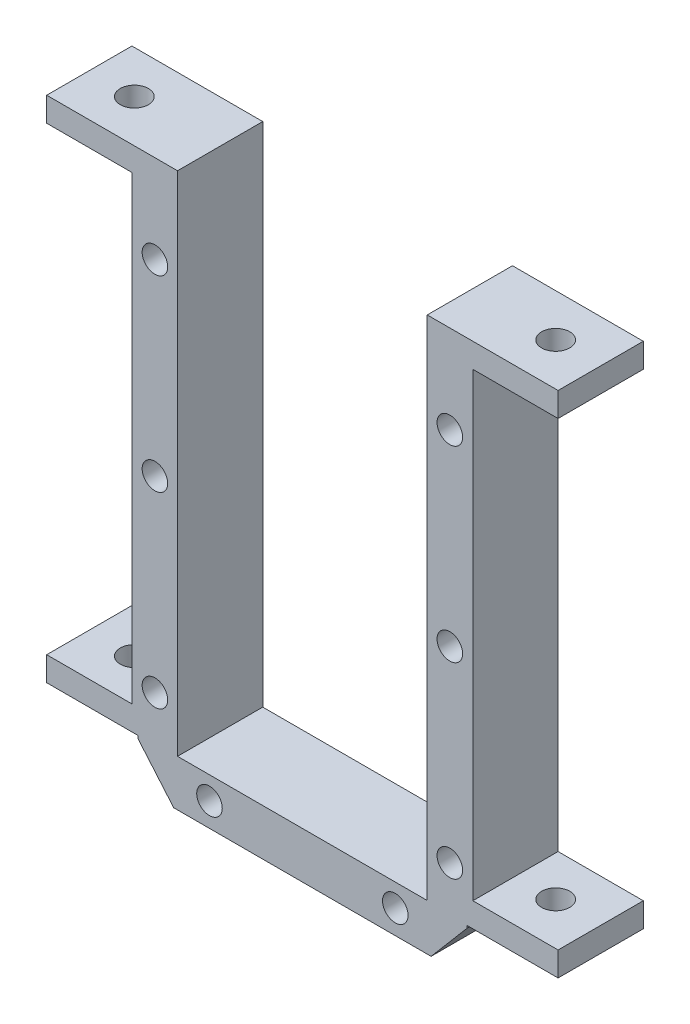
SolidWorks part; units mm, degrees
material "AISI 1035 Acier (SS)"
ref_plane "Front Plane" through (0, 0, 0) normal (0, 0, 1) x (1, 0, 0)
ref_plane "Top Plane" through (0, 0, 0) normal (0, 1, 0) x (1, 0, 0)
ref_plane "Right Plane" through (0, 0, 0) normal (1, 0, 0) x (0, 0, -1)
sketch "Sketch1" plane through (0, 0, 0) normal (0, 0, 1) x (1, 0, 0)
  line L1 (-20.1, 32.55) -> (19.9, 32.55)
  line L2 (-20.1, 32.55) -> (-20.1, -32.55)
  line L3 (-20.1, -32.55) -> (19.9, -32.55)
  line L4 (19.9, 32.55) -> (19.9, -32.55)
  point P0 (0, 0)
  dimension "D1" = 40
  dimension "D2" = 65.1
extrude "Boss-Extrude1" add sketch "Sketch1" along normal blind 10
sketch "Sketch2" plane through (0, 0, 10) normal (0, 0, 1) x (1, 0, 0)
  line L0 (-0.1, 32.55) -> (-0.1, -32.55) construction
  line L1 (19.9, 32.55) -> (-20.1, 32.55) construction
  line L2 (-20.1, -32.55) -> (19.9, -32.55) construction
  line L3 (-20.1, 0) -> (19.9, 0) construction
  line L4 (-20.1, 32.55) -> (-20.1, -32.55) construction
  line L5 (19.9, -32.55) -> (19.9, 32.55) construction
  line L6 (-20.1, -27.45) -> (19.9, -27.45) construction
  line L7 (15, -32.55) -> (19.335, -27.45)
  line L8 (19.335, -27.45) -> (15, -32.55) construction
  line L9 (19.335, -27.45) -> (19.9, -27.45)
  line L22 (19.9, -27.45) -> (19.9, -32.55)
  line L23 (19.9, -32.55) -> (15, -32.55)
  line L24 (-20.1, -27.45) -> (-20.1, -32.55)
  line L25 (-19.535, -27.45) -> (-20.1, -27.45)
  line L26 (-15.2, -32.55) -> (-19.535, -27.45)
  line L27 (-20.1, -32.55) -> (-15.2, -32.55)
  point P12 (-0.1, -27.45)
  point P13 (-19.535, -27.45)
  point P17 (-0.1, -27.45)
  point P18 (19.335, -27.45)
  dimension "D1" = 60
extrude "Cut-Extrude1" cut sketch "Sketch2" against normal blind 10
sketch "Sketch4" plane through (0, 0, 10) normal (0, 0, 1) x (1, 0, 0)
  line L0 (-0.1, 32.55) -> (-0.1, -32.55) construction
  line L1 (19.9, 32.55) -> (-20.1, 32.55) construction
  line L2 (-15.2, -32.55) -> (15, -32.55) construction
  line L3 (-20.1, 2.55) -> (19.9, 2.55) construction
  line L4 (-20.1, 32.55) -> (-20.1, -27.45) construction
  line L5 (19.9, -27.45) -> (19.9, 32.55) construction
  line L6 (14.55, -26.95) -> (-14.75, -26.95) construction
  line L7 (-14.75, -26.95) -> (-14.75, 32.55) construction
  line L8 (14.55, -26.95) -> (14.55, 32.55) construction
  line L9 (-14.75, 32.55) -> (-14.75, -26.95)
  line L10 (-14.75, -26.95) -> (14.55, -26.95)
  line L11 (14.55, -26.95) -> (14.55, 32.55)
  line L12 (14.55, 32.55) -> (-14.75, 32.55)
  point P12 (-0.1, -26.95)
  point P16 (-0.1, -26.95)
  dimension "D1" = 5.6
  dimension "D2" = 29.3
extrude "Cut-Extrude2" cut sketch "Sketch4" against normal blind 10
sketch "Sketch5" plane through (0, 0, 10) normal (0, 0, 1) x (1, 0, 0)
  line L0 (-14.75, 32.55) -> (14.55, 32.55) construction
  line L1 (-0.1, 32.55) -> (-0.1, -32.55) construction
  line L2 (-15.2, -32.55) -> (15, -32.55) construction
  line L3 (-15.2, -32.55) -> (15, -32.55) construction
  line L6 (-20.1, 32.55) -> (-20.1, -27.45) construction
  circle A0 centre (-17.4, 22.05) radius 1.5
  circle A1 centre (-17.4, 0.05) radius 1.5
  circle A2 centre (-17.4, -21.95) radius 1.5
  circle A3 centre (-11, -29.75) radius 1.5
  circle A4 centre (10.8, -29.75) radius 1.5
  circle A5 centre (17.2, -21.95) radius 1.5
  circle A6 centre (17.2, 0.05) radius 1.5
  circle A7 centre (17.2, 22.05) radius 1.5
  point P8 (-17.4, 22.05)
  point P9 (-17.4, 0.05)
  point P10 (-17.4, -21.95)
  point P11 (-11, -29.75)
  point P22 (10.8, -29.75)
  point P25 (17.2, -21.95)
  point P28 (17.2, 0.05)
  point P31 (17.2, 22.05)
  dimension "D6" = 3
  dimension "D7" = 3
  dimension "D8" = 3
  dimension "D9" = 3
  dimension "D1" = 10.6
  dimension "D2" = 32.6
  dimension "D3" = 54.6
  dimension "D4" = 2.8
  dimension "D5" = 9.1
  dimension "D10" = 17.3
  dimension "D11" = 17.3
  dimension "D12" = 17.3
extrude "Cut-Extrude3" cut sketch "Sketch5" against normal blind 10
sketch "Sketch6" plane through (0, 0, 10) normal (0, 0, 1) x (1, 0, 0)
  line L0 (-14.75, 32.55) -> (14.55, 32.55) construction
  line L1 (-0.1, 32.55) -> (-0.1, -32.55) construction
  line L2 (-15.2, -32.55) -> (15, -32.55) construction
  line L3 (-20.1, 2.55) -> (19.9, 2.55) construction
  line L4 (-20.1, 32.55) -> (-20.1, -27.45) construction
  line L5 (19.9, -27.45) -> (19.9, 32.55) construction
sketch "Sketch7" plane through (19.9, 0, 0) normal (1, 0, 0) x (0, 0, -1)
  line L0 (0, 2.55) -> (-10, 2.55) construction
  line L1 (-10, 32.55) -> (-10, -32.55) construction
  line L2 (0, -27.45) -> (0, 32.55) construction
  line L3 (0, 29.55) -> (-10, 29.55)
  line L4 (-10, 29.55) -> (-10, 32.55)
  line L5 (-10, 32.55) -> (0, 32.55)
  line L6 (0, 32.55) -> (0, 29.55)
  line L7 (-10, -27.45) -> (-10, 32.55) construction
  line L8 (-10, -27.45) -> (0, -27.45)
  line L9 (-10, -24.45) -> (-10, -27.45)
  line L10 (0, -24.45) -> (-10, -24.45)
  line L11 (0, -27.45) -> (0, -24.45)
  point P5 (0, 29.55)
  dimension "D1" = 3
extrude "Boss-Extrude2" add sketch "Sketch7" along normal blind 10
sketch "Sketch8" plane through (-20.1, 0, 0) normal (-1, 0, 0) x (0, 0, 1)
  line L0 (0, 2.55) -> (10, 2.55) construction
  line L1 (0, 32.55) -> (0, -27.45) construction
  line L2 (10, 32.55) -> (10, -32.55) construction
  line L3 (0, 29.55) -> (10, 29.55)
  line L4 (10, 29.55) -> (10, 32.55)
  line L5 (10, 32.55) -> (0, 32.55)
  line L6 (0, 32.55) -> (0, 29.55)
  line L7 (10, -27.45) -> (0, -27.45)
  line L8 (10, -24.45) -> (10, -27.45)
  line L9 (0, -24.45) -> (10, -24.45)
  line L10 (0, -27.45) -> (0, -24.45)
  point P6 (0, 29.55)
  dimension "D1" = 3
extrude "Boss-Extrude3" add sketch "Sketch8" along normal blind 10
sketch "Sketch9" plane through (0, -27.45, 0) normal (0, -1, 0) x (-1, 0, 0)
  line L0 (24.8175, -10) -> (24.8175, 0) construction
  line L1 (19.535, -10) -> (30.1, -10) construction
  line L2 (19.535, 0) -> (30.1, 0) construction
  line L3 (30.1, -5) -> (19.535, -5) construction
  line L4 (30.1, 0) -> (30.1, -10) construction
  line L5 (19.535, 0) -> (19.535, -10) construction
  circle A0 centre (24.8175, -5) radius 1.65
  dimension "D1" = 3.3
extrude "Cut-Extrude4" cut sketch "Sketch9" against normal through all
sketch "Sketch10" plane through (0, -27.45, 0) normal (0, -1, 0) x (-1, 0, 0)
  line L0 (-24.6175, -10) -> (-24.6175, 0) construction
  line L1 (-29.9, -10) -> (-19.335, -10) construction
  line L2 (-29.9, 0) -> (-19.335, 0) construction
  line L3 (-19.335, -5) -> (-29.9, -5) construction
  line L4 (-19.335, 0) -> (-19.335, -10) construction
  line L5 (-29.9, -10) -> (-29.9, 0) construction
  circle A0 centre (-24.6175, -5) radius 1.65
  dimension "D1" = 3.3
extrude "Cut-Extrude5" cut sketch "Sketch10" against normal through all
sketch "Esquisse1" plane through (0, 0, 10) normal (0, 0, 1) x (1, 0, 0)
  line L6 (29.9, -27.45) -> (29.9, -27.3)
  line L7 (29.9, -24.45) -> (29.9, -27.45) construction
  line L8 (29.9, -27.3) -> (19.335, -27.3)
  line L9 (19.335, -27.3) -> (19.185, -27.3)
  line L10 (29.9, 32.55) -> (29.9, 32.4)
  line L11 (19.185, -27.3) -> (19.185, -27.9056)
  line L12 (19.185, -27.9056) -> (27.185, -27.9056)
  line L14 (29.9, 32.55) -> (29.9, 29.55) construction
  line L15 (29.9, 32.4) -> (14.55, 32.4)
  line L16 (14.55, -26.95) -> (14.55, 32.55) construction
  line L17 (14.55, 32.4) -> (14.55, 32.55)
  line L18 (14.55, 32.55) -> (29.9, 32.55)
  line L31 (27.185, -27.9056) -> (27.185, -27.45)
  line L32 (29.9, -27.45) -> (19.335, -27.45) construction
  line L33 (27.185, -27.45) -> (29.9, -27.45)
  line L34 (-15.2, -32.55) -> (15, -32.55) construction
  line L35 (-0.1, -32.55) -> (-0.1, -23.8847) construction
  line L36 (-27.385, -27.9056) -> (-27.385, -27.45)
  line L37 (-19.385, -27.9056) -> (-27.385, -27.9056)
  line L38 (-19.385, -27.3) -> (-19.385, -27.9056)
  line L39 (-19.535, -27.3) -> (-19.385, -27.3)
  line L40 (-30.1, -27.3) -> (-19.535, -27.3)
  line L41 (-30.1, -27.45) -> (-30.1, -27.3)
  line L42 (-27.385, -27.45) -> (-30.1, -27.45)
  line L43 (-14.75, 32.4) -> (-14.75, 32.55)
  line L44 (-30.1, 32.4) -> (-14.75, 32.4)
  line L45 (-30.1, 32.55) -> (-30.1, 32.4)
  line L46 (-14.75, 32.55) -> (-30.1, 32.55)
  line L47 (-14.75, -26.95) -> (14.55, -26.95)
  line L48 (-14.75, -26.95) -> (-14.75, -27.1)
  line L49 (-14.75, -27.1) -> (14.55, -27.1)
  line L50 (14.55, -26.95) -> (14.55, -27.1)
  dimension "D1" = 0.15
  dimension "D2" = 0.15
  dimension "D3" = 0.6056
  dimension "D4" = 8
  dimension "D5" = 0.15
  dimension "D6" = 2.715
  dimension "D7" = 15.1
  dimension "D8" = 0.15
extrude "Enlèv. mat.-Extru.1" cut sketch "Esquisse1" against normal through all
